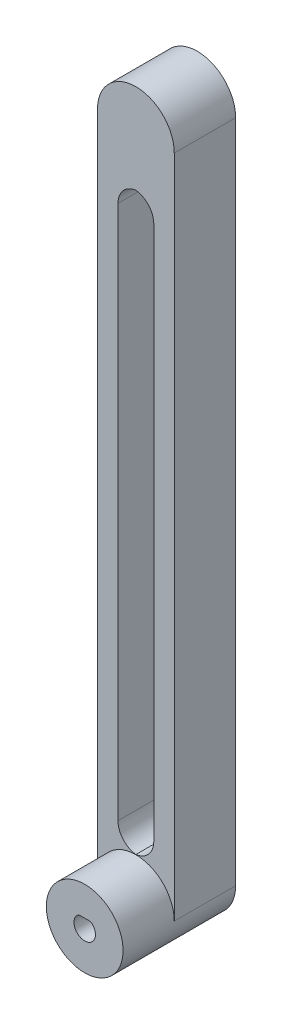
SolidWorks part; units mm, degrees
ref_plane "Front Plane" through (0, 0, 0) normal (0, 0, 1) x (1, 0, 0)
ref_plane "Top Plane" through (0, 0, 0) normal (0, 1, 0) x (1, 0, 0)
ref_plane "Right Plane" through (0, 0, 0) normal (1, 0, 0) x (0, 0, -1)
sketch "Sketch1" plane through (0, 0, 0) normal (0, 0, 1) x (1, 0, 0)
  line L0 (-5.6452, 102.5806) -> (-5.6452, -27.4194)
  line L1 (9.3548, 102.5806) -> (9.3548, -27.4194)
  arc A0 (-5.6452, 102.5806) -> (9.3548, 102.5806) centre (1.8548, 102.5806) cw
  arc A1 (-5.6452, -27.4194) -> (9.3548, -27.4194) centre (1.8548, -27.4194) ccw
  dimension "D1" = 15
  dimension "D2" = 130
extrude "Boss-Extrude1" add sketch "Sketch1" along normal blind 12
sketch "Sketch2" plane through (0, 0, 12) normal (0, 0, 1) x (1, 0, 0)
  line L0 (-5.6452, -27.4194) -> (9.3548, -27.4194) construction
  circle A0 centre (1.8548, -27.4194) radius 3.1
extrude "Boss-Extrude2" add sketch "Sketch2" along normal blind 15
sketch "Sketch3" plane through (0, 0, 27) normal (0, 0, 1) x (1, 0, 0)
  line L0 (0.1666, -24.8194) -> (3.543, -24.8194)
  circle A0 centre (1.8548, -27.4194) radius 3.1 construction
  circle A1 centre (1.8548, -27.4194) radius 3.1 construction
  arc A2 (0.1666, -24.8194) -> (3.543, -24.8194) centre (1.8548, -27.4194) ccw
  dimension "3.6" = 2.6
extrude "Cut-Extrude1" cut sketch "Sketch3" against normal blind 50
sketch "Sketch4" plane through (0, 0, 27) normal (0, 0, 1) x (1, 0, 0)
  line L0 (0.1666, -24.8194) -> (3.543, -24.8194)
  arc A0 (0.1666, -24.8194) -> (3.543, -24.8194) centre (1.8548, -27.4194) cw
extrude "Cut-Extrude2" cut sketch "Sketch4" against normal blind 15
sketch "Sketch5" plane through (0, 0, 12) normal (0, 0, 1) x (1, 0, 0)
  line L0 (-5.6452, 102.5806) -> (-5.6452, -27.4194) construction
  line L1 (-1.6452, -19.9194) -> (-5.6452, -19.9194) construction
  line L2 (-1.6452, -19.9194) -> (-1.6452, 92.5806) construction
  line L3 (-1.6452, 92.5806) -> (-5.6452, 92.5806) construction
  line L4 (-5.6452, -19.9194) -> (-5.6452, 92.5806) construction
  line L6 (5.3548, -19.9194) -> (9.3548, -19.9194) construction
  line L7 (5.3548, -19.9194) -> (5.3548, 92.5806) construction
  line L8 (5.3548, 92.5806) -> (9.3548, 92.5806) construction
  line L9 (9.3548, -19.9194) -> (9.3548, 92.5806) construction
  line L10 (-1.6452, 92.5806) -> (5.3548, 92.5806)
  line L11 (-1.6452, 92.5806) -> (-1.6452, -19.9194)
  line L12 (-1.6452, -19.9194) -> (5.3548, -19.9194)
  line L13 (5.3548, 92.5806) -> (5.3548, -19.9194)
  arc A0 (-5.6452, -27.4194) -> (9.3548, -27.4194) centre (1.8548, -27.4194) cw construction
  arc A1 (9.3548, 102.5806) -> (-5.6452, 102.5806) centre (1.8548, 102.5806) ccw construction
  dimension "D1" = 4
  dimension "D2" = 4
  dimension "D3" = 10
extrude "Cut-Extrude3" cut sketch "Sketch5" against normal blind 12
sketch "Sketch6" plane through (-5.6452, 0, 0) normal (-1, 0, 0) x (0, 0, 1)
  line L0 (6, 102.5806) -> (6, 14.8619) construction
  line L1 (12, 102.5806) -> (0, 102.5806) construction
  circle A0 centre (6, 78.769) radius 5.15
  circle A1 centre (6, 53.769) radius 5.15
  circle A2 centre (6, 28.769) radius 5.15
  dimension "D1" = 3
extrude "Cut-Extrude4" cut sketch "Sketch6" against normal blind 2
fillet "Fillet1" radius 4 4 edges at (-1.6452, -19.9194, 6) (5.3548, -19.9194, 6) (5.3548, 92.5806, 6) (-1.6452, 92.5806, 6)
sketch "Sketch7" plane through (0, 0, 12) normal (0, 0, 1) x (1, 0, 0)
  arc A0 (-5.6452, -27.4194) -> (9.3548, -27.4194) centre (1.8548, -27.4194) ccw
  arc A1 (-5.6452, -27.4194) -> (9.3548, -27.4194) centre (1.8548, -27.4194) ccw construction
  arc A2 (-5.6452, -27.4194) -> (9.3548, -27.4194) centre (1.8548, -27.4194) cw
extrude "Boss-Extrude3" add sketch "Sketch7" along normal blind 10
sketch "Sketch9" plane through (0, 0, 22) normal (0, 0, 1) x (1, 0, 0)
  circle A0 centre (1.8548, -27.4194) radius 2.1
extrude "Cut-Extrude5" cut sketch "Sketch9" against normal blind 7
sketch "Sketch10" plane through (0, 0, 22) normal (0, 0, 1) x (1, 0, 0)
  line L0 (0.694, -25.6694) -> (3.0157, -25.6694)
  line L1 (1.8548, -29.5194) -> (1.8548, -27.4194) construction
  circle A0 centre (1.8548, -27.4194) radius 2.1 construction
  circle A1 centre (1.8548, -27.4194) radius 2.1 construction
  arc A2 (0.694, -25.6694) -> (3.0157, -25.6694) centre (1.8548, -27.4194) cw
  dimension "D1" = 1.75
extrude "Boss-Extrude4" add sketch "Sketch10" against normal blind 7
